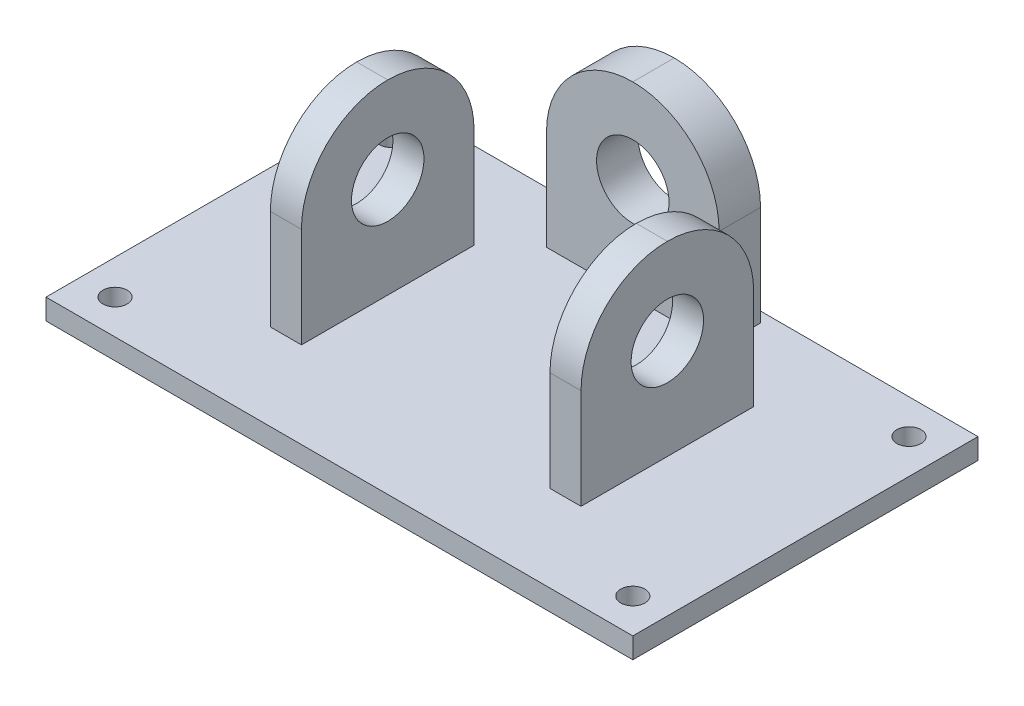
SolidWorks part; units mm, degrees
material "uhlíková ocel 7850"
ref_plane "Přední rovina" through (0, 0, 0) normal (0, 0, 1) x (1, 0, 0)
ref_plane "Horní rovina" through (0, 0, 0) normal (0, 1, 0) x (1, 0, 0)
ref_plane "Pravá rovina" through (0, 0, 0) normal (1, 0, 0) x (0, 0, -1)
sketch "Skica1" plane through (0, 0, 0) normal (0, 1, 0) x (1, 0, 0)
  line L1 (-42.5, -25) -> (42.5, -25)
  line L2 (-42.5, -25) -> (-42.5, 25)
  line L3 (-42.5, 25) -> (42.5, 25)
  line L4 (42.5, -25) -> (42.5, 25)
  line L5 (-42.5, -25) -> (42.5, 25) construction
  line L6 (-42.5, 25) -> (42.5, -25) construction
  point P0 (0, 0)
  dimension "D1" = 85
  dimension "D2" = 50
extrude "Přidat vysunutím1" add sketch "Skica1" along normal blind 3
sketch "Skica2" plane through (0, 3, 0) normal (0, 1, 0) x (1, 0, 0)
  line L0 (-20.25, 0) -> (0, 0) construction
  line L1 (-22.5, 12.5) -> (-18, 12.5)
  line L2 (-22.5, 12.5) -> (-22.5, -12.5)
  line L3 (-22.5, -12.5) -> (-18, -12.5)
  line L4 (-18, 12.5) -> (-18, -12.5)
  line L5 (-22.5, 12.5) -> (-18, -12.5) construction
  line L6 (-22.5, -12.5) -> (-18, 12.5) construction
  line L8 (0, 0) -> (0, 20.5) construction
  line L9 (-12.5, 17.5) -> (12.5, 17.5)
  line L10 (-12.5, 17.5) -> (-12.5, 23.5)
  line L11 (-12.5, 23.5) -> (12.5, 23.5)
  line L12 (12.5, 17.5) -> (12.5, 23.5)
  line L13 (-12.5, 17.5) -> (12.5, 23.5) construction
  line L14 (-12.5, 23.5) -> (12.5, 17.5) construction
  line L15 (22.5, -12.5) -> (18, 12.5) construction
  line L16 (22.5, 12.5) -> (18, -12.5) construction
  line L17 (18, 12.5) -> (18, -12.5)
  line L18 (22.5, -12.5) -> (18, -12.5)
  line L19 (22.5, 12.5) -> (22.5, -12.5)
  line L20 (22.5, 12.5) -> (18, 12.5)
  point P0 (-20.25, 0)
  point P10 (0, 20.5)
  point P20 (20.25, 0)
  dimension "D1" = 4.5
  dimension "D2" = 25
  dimension "D3" = 18
  dimension "D4" = 6
  dimension "D5" = 25
  dimension "D6" = 20.5
extrude "Přidat vysunutím2" add sketch "Skica2" along normal blind 27
fillet "Zaoblit1" radius 12.5 6 edges at (-20.25, 30, -12.5) (-20.25, 30, 12.5) (-12.5, 30, -20.5) (12.5, 30, -20.5) (20.25, 30, -12.5) (20.25, 30, 12.5)
sketch "Skica3" plane through (-22.5, 0, 0) normal (-1, 0, 0) x (0, 0, 1)
  circle A0 centre (0, 17.5) radius 5.25
  dimension "D1" = 10.5
extrude "Odebrat vysunutím1" cut sketch "Skica3" against normal through all
sketch "Skica4" plane through (0, 0, -17.5) normal (0, 0, 1) x (1, 0, 0)
  circle A0 centre (0, 17.5) radius 5.25
  dimension "D1" = 10.5
extrude "Odebrat vysunutím2" cut sketch "Skica4" against normal through all
sketch "Skica5" plane through (0, 3, 0) normal (0, 1, 0) x (1, 0, 0)
  line L1 (37.5, 20) -> (-37.5, 20) construction
  line L2 (37.5, 20) -> (37.5, -20) construction
  line L3 (37.5, -20) -> (-37.5, -20) construction
  line L4 (-37.5, 20) -> (-37.5, -20) construction
  line L5 (37.5, 20) -> (-37.5, -20) construction
  line L6 (37.5, -20) -> (-37.5, 20) construction
  point P0 (0, 0)
  dimension "D1" = 40
  dimension "D2" = 75
hole_wizard "Díry pro kolík, velikost mm1" positions "Skica7" profile "Skica6" hole size "Ø3.0" standard "ISO"
sketch "Skica7" plane through (0, 3, 0) normal (0, 1, 0) x (1, 0, 0)
  point P0 (-37.5, 20)
  point P3 (37.5, 20)
  point P6 (37.5, -20)
  point P9 (-37.5, -20)
sketch "Skica6" plane through (-37.5, 3, -20) normal (1, 0, 0) x (0, 0, 1)
  line L0 (0, 0) -> (0, 11.0515)
  line L1 (0, 11.0515) -> (1.75, 10)
  line L2 (1.75, 10) -> (1.75, 0)
  line L5 (1.75, 0) -> (0, 0)
  line L10 (0, 11.0515) -> (-1.75, 10) construction
  line L11 (0, -6.35) -> (0, 107.95) construction
  dimension "Průměr díry" = 3.5
  dimension "Hloubka díry" = 10
  dimension "Úhel vrtání" = 118
